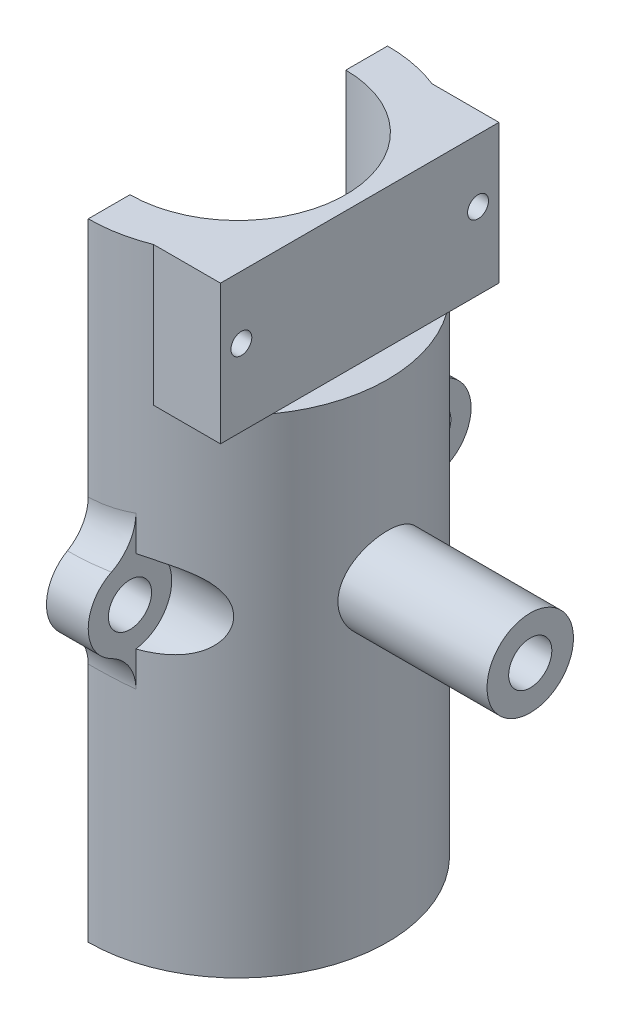
SolidWorks part; units mm, degrees
ref_plane "Front Plane" through (0, 0, 0) normal (0, 0, 1) x (1, 0, 0)
ref_plane "Top Plane" through (0, 0, 0) normal (0, 1, 0) x (1, 0, 0)
ref_plane "Right Plane" through (0, 0, 0) normal (1, 0, 0) x (0, 0, -1)
sketch "Sketch10" plane through (0, 0, 0) normal (0, 1, 0) x (1, 0, 0)
  circle A0 centre (0, 0) radius 10.75
  dimension "D1" = 21.5
extrude "Boss-Extrude4" add sketch "Sketch10" along normal blind 22.5 and the other way blind 22.5
sketch "Sketch11" plane through (0, 0, 0) normal (1, 0, 0) x (0, 0, -1)
  circle A0 centre (0, 0) radius 3.105
  dimension "D1" = 6.21
extrude "Boss-Extrude5" add sketch "Sketch11" along normal blind 21
sketch "Sketch14" plane through (0, 22.5, 0) normal (0, 1, 0) x (1, 0, 0)
  line L0 (-14, 13.0628) -> (0, 13.0628)
  line L1 (-14, 13.0628) -> (-14, -13.0628)
  line L2 (0, 13.0628) -> (0, -13.0628)
  line L3 (-14, -13.0628) -> (0, -13.0628)
  line L4 (-14, 13.0628) -> (0, -13.0628) construction
  line L5 (0, 13.0628) -> (-14, -13.0628) construction
  point P1 (-7, 0)
extrude "Cut-Extrude4" cut sketch "Sketch14" against normal blind 45
sketch "Sketch15" plane through (0, 0, 0) normal (-1, 0, 0) x (0, 0, 1)
  line L0 (10.75, -22.5) -> (10.75, 22.5) construction
  line L1 (-10.75, 22.5) -> (-10.75, -22.5) construction
  circle A2 centre (10.75, 0) radius 3
  circle A3 centre (-10.75, 0) radius 3
  dimension "D1" = 6
  dimension "D2" = 6
sketch "Sketch16" plane through (21, 0, 0) normal (1, 0, 0) x (0, 0, -1)
  circle A0 centre (0, 0) radius 1.55
  dimension "D1" = 3.1
extrude "Cut-Extrude6" cut sketch "Sketch16" against normal blind 8 contours A0
extrude "Boss-Extrude8" add sketch "Sketch15" against normal blind 3
sketch "Sketch17" plane through (0, 0, 0) normal (-1, 0, 0) x (0, 0, 1)
  circle A0 centre (10.75, 0) radius 1.55
  circle A1 centre (-10.75, 0) radius 1.55
  dimension "D1" = 3.1
  dimension "D2" = 3.1
extrude "Cut-Extrude8" cut sketch "Sketch17" against normal blind 6
sketch "Sketch18" plane through (3, 0, 0) normal (1, 0, 0) x (0, 0, -1)
  circle A0 centre (-10.75, 0) radius 3
  circle A1 centre (10.75, 0) radius 3
extrude "Cut-Extrude9" cut sketch "Sketch18" along normal blind 6
fillet "Fillet5" radius 3 4 edges
sketch "Sketch21" plane through (0, 0, 0) normal (1, 0, 0) x (0, 0, -1)
  line L0 (-10.75, 22.5) -> (10.75, 22.5) construction
  line L1 (10, 12.5) -> (-10, 12.5)
  line L2 (10, 12.5) -> (10, 22.5)
  line L3 (10, 22.5) -> (-10, 22.5)
  line L4 (-10, 12.5) -> (-10, 22.5)
  line L5 (10, 12.5) -> (-10, 22.5) construction
  line L6 (10, 22.5) -> (-10, 12.5) construction
  point P0 (0, 17.5)
  dimension "D1" = 10
  dimension "D2" = 10
extrude "Boss-Extrude9" add sketch "Sketch21" along normal blind 8.75
sketch "Sketch12" plane through (0, 22.5, 0) normal (0, 1, 0) x (1, 0, 0)
  circle A0 centre (0, 0) radius 7.75
  dimension "D1" = 15.5
extrude "Cut-Extrude3" cut sketch "Sketch12" against normal blind 45
sketch "Sketch22" plane through (8.75, 0, 0) normal (1, 0, 0) x (0, 0, -1)
  line L0 (10, 12.5) -> (10, 22.5) construction
  line L2 (6.245, 12.5) -> (10, 12.5) construction
  circle A0 centre (8.5, 18) radius 0.75
  circle A1 centre (-8.5, 18) radius 0.75
  dimension "D1" = 1.5
  dimension "D2" = 1.5
  dimension "D3" = 17
  dimension "D4" = 1.5
  dimension "D5" = 5.5
extrude "Cut-Extrude10" cut sketch "Sketch22" against normal blind 4
sketch "Sketch23" plane through (8.75, 0, 0) normal (1, 0, 0) x (0, 0, -1)
  line L1 (6.245, 12.5) -> (-6.245, 12.5)
  line L2 (6.245, 12.5) -> (6.245, 22.5)
  line L3 (6.245, 22.5) -> (-6.245, 22.5)
  line L4 (-6.245, 12.5) -> (-6.245, 22.5)
extrude "Cut-Extrude11" cut sketch "Sketch23" along normal blind 2
